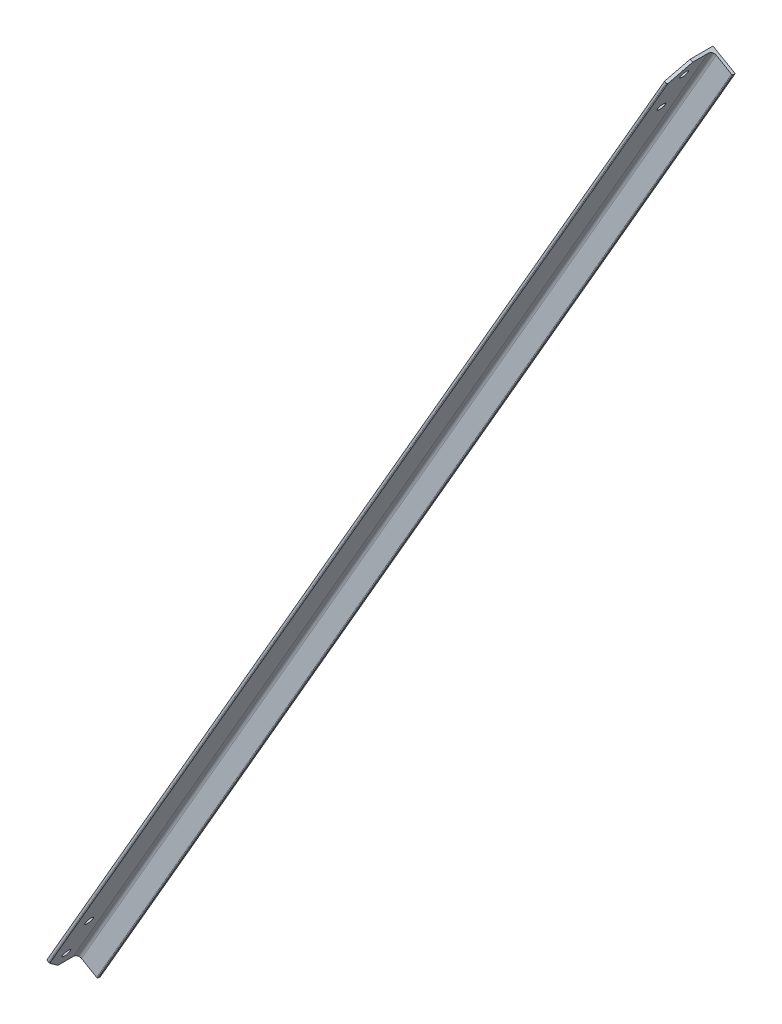
SolidWorks part; units mm, degrees
material "普通碳钢"
ref_plane "前视基准面" through (0, 0, 0) normal (0, 0, 1) x (1, 0, 0)
ref_plane "上视基准面" through (0, 0, 0) normal (0, 1, 0) x (1, 0, 0)
ref_plane "右视基准面" through (0, 0, 0) normal (1, 0, 0) x (0, 0, -1)
sketch "草图1" plane through (0, 0, 0) normal (0, 0, 1) x (1, 0, 0)
  line L0 (0, 0) -> (1115, 1931.2367) construction
  line L1 (0, 0) -> (171.8941, 0) construction
  line L2 (1115, 1931.2367) -> (0, 0)
  dimension "D1" = 60
  dimension "D2" = 2230
other "不等边角钢 70X45X5(1)"
ref_plane "基准面1" through (1115, 1931.2367, 0) normal (-0.5, -0.866, 0) x (0.866, -0.5, 0)
sketch "草图11" plane through (1115, 1931.2367, 0) normal (-0.5, -0.866, 0) x (0.866, -0.5, 0)
  line L0 (0, 70) -> (0, 0)
  line L1 (0, 0) -> (45, 0)
  line L2 (45, 0) -> (45, 3.33)
  line L3 (43.33, 5) -> (12.5, 5)
  line L4 (5, 12.5) -> (5, 68.33)
  line L5 (3.33, 70) -> (0, 70)
  arc A0 (12.5, 5) -> (5, 12.5) centre (12.5, 12.5) cw
  arc A1 (45, 3.33) -> (43.33, 5) centre (43.33, 3.33) ccw
  arc A2 (5, 68.33) -> (3.33, 70) centre (3.33, 68.33) ccw
  point P8 (5, 70)
  point P9 (0, 70)
  point P10 (0, 0)
  point P11 (45, 0)
  point P12 (45, 5)
  point P16 (45, 5)
  point P19 (5, 70)
  point P20 (0, 0)
  dimension "D5" = 7.5
  dimension "D6" = 1.67
  dimension "D1" = 45
  dimension "D2" = 70
  dimension "D3" = 5
  dimension "D4" = 5
sketch "草图12" plane through (0, 0, 0) normal (-0.866, 0.5, 0) x (0, 0, 1)
  line L0 (40, 0) -> (40, 182.7203) construction
  line L1 (70, 0) -> (0, 0) construction
  line L2 (70, 0) -> (70, 2230) construction
  line L3 (118.7853, 30) -> (40, 30) construction
  line L4 (118.7853, 110) -> (40, 110) construction
  circle A0 centre (40, 30) radius 7
  circle A1 centre (40, 110) radius 7
  dimension "D3" = 80
  dimension "D4" = 14
  dimension "D5" = 14
  dimension "D1" = 30
  dimension "D2" = 30
extrude "切除-拉伸1" cut sketch "草图12" against normal up to next
sketch "草图13" plane through (0, 0, 0) normal (-0.866, 0.5, 0) x (0, 0, 1)
  line L1 (40.0047, 2200) -> (40.0047, 2120) construction
  line L2 (70, 0) -> (70, 2230) construction
  line L3 (40.0047, 2200) -> (66.8756, 2200) construction
  line L4 (40.0047, 2120) -> (60.9865, 2120) construction
  line L5 (70, 2230) -> (0, 2230) construction
  circle A0 centre (40.0047, 2120) radius 7
  circle A1 centre (40.0047, 2200) radius 7
  dimension "D1" = 29.9953
  dimension "D2" = 30
  dimension "D3" = 80
extrude "切除-拉伸2" cut sketch "草图13" against normal up to next
chamfer "倒角1" distance 30 1 edges at (1116.4419, 1930.4042, 70)
chamfer "倒角2" distance 30 1 edges at (1.4419, -0.8325, 70)
